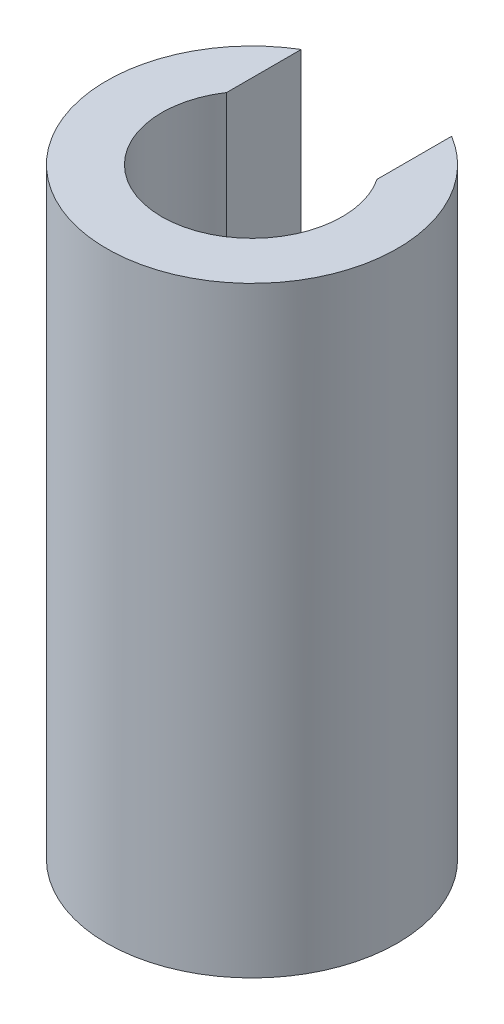
SolidWorks part; units mm, degrees
ref_plane "Front Plane" through (0, 0, 0) normal (0, 0, 1) x (1, 0, 0)
ref_plane "Top Plane" through (0, 0, 0) normal (0, 1, 0) x (1, 0, 0)
ref_plane "Right Plane" through (0, 0, 0) normal (1, 0, 0) x (0, 0, -1)
sketch "Sketch1" plane through (0, 0, 0) normal (0, 1, 0) x (1, 0, 0)
  circle A0 centre (0, 0) radius 2.9
  circle A1 centre (0, 0) radius 1.8
  dimension "D1" = 5.8
  dimension "D2" = 3.6
extrude "Boss-Extrude1" add sketch "Sketch1" along normal blind 12 contours A0
sketch "Sketch3" plane through (0, 0, 0) normal (0, -1, 0) x (1, 0, 0)
  circle A0 centre (0, 0) radius 1.8
  dimension "D1" = 3.6
extrude "Cut-Extrude1" cut sketch "Sketch3" against normal blind 12
sketch "Sketch4" plane through (0, 12, 0) normal (0, 1, 0) x (1, 0, 0)
  line L1 (1.5, 0) -> (-1.5, 0)
  line L2 (1.5, 0) -> (1.5, 2.9)
  line L3 (1.5, 2.9) -> (-1.5, 2.9)
  line L4 (-1.5, 0) -> (-1.5, 2.9)
  circle A0 centre (0, 0) radius 2.9 construction
  point P4 (0, 0)
  dimension "D1" = 3
extrude "Cut-Extrude2" cut sketch "Sketch4" against normal blind 6
